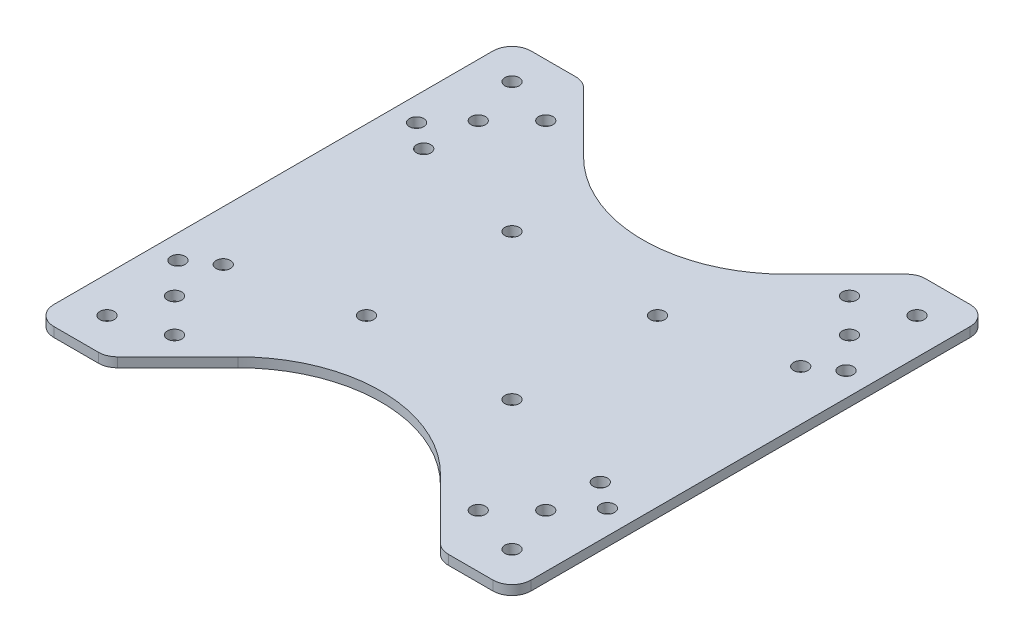
SolidWorks part; units mm, degrees
material "Thornel Mat VMA"
ref_plane "前视基准面" through (0, 0, 0) normal (0, 0, 1) x (1, 0, 0)
ref_plane "上视基准面" through (0, 0, 0) normal (0, 1, 0) x (1, 0, 0)
ref_plane "右视基准面" through (0, 0, 0) normal (1, 0, 0) x (0, 0, -1)
other "Configuration Table"
sketch "草图1" plane through (0, 0, 0) normal (0, 1, 0) x (1, 0, 0)
  line L1 (-50, -50) -> (50, -50)
  line L2 (-50, -50) -> (-50, 50)
  line L3 (-50, 50) -> (50, 50)
  line L4 (50, -50) -> (50, 50)
  line L5 (-50, -50) -> (50, 50) construction
  line L6 (-50, 50) -> (50, -50) construction
  point P0 (0, 0)
  dimension "D1" = 100
  dimension "D2" = 100
extrude "凸台-拉伸1" add sketch "草图1" along normal blind 2
sketch "草图3" plane through (0, 2, 0) normal (0, 1, 0) x (1, 0, 0)
  line L0 (-1000, 0) -> (49000, 0) construction
  line L1 (-42.4264, 42.4264) -> (0, 0) construction
  line L2 (-42.9749, 27.7358) -> (35312.3642, 35383.0749) construction
  line L3 (0, -1000) -> (0, 49000) construction
  circle A0 centre (0, 0) radius 60 construction
  circle A1 centre (-42.4264, 42.4264) radius 1.5
  circle A2 centre (-31.8198, 38.8909) radius 1.5
  circle A3 centre (-38.8909, 31.8198) radius 1.5
  circle A4 centre (-31.8198, -38.8909) radius 1.5
  circle A5 centre (-38.8909, -31.8198) radius 1.5
  circle A6 centre (-42.4264, -42.4264) radius 1.5
  circle A7 centre (31.8198, 38.8909) radius 1.5
  circle A8 centre (38.8909, 31.8198) radius 1.5
  circle A9 centre (42.4264, 42.4264) radius 1.5
  circle A10 centre (31.8198, -38.8909) radius 1.5
  circle A11 centre (42.4264, -42.4264) radius 1.5
  circle A12 centre (38.8909, -31.8198) radius 1.5
  dimension "D1" = 120
  dimension "D3" = 3
  dimension "D6" = 3
  dimension "D7" = 3
  dimension "D8" = 5
  dimension "D9" = 5
  dimension "D2" = 45
  dimension "D4" = 90
  dimension "D5" = 10
extrude "切除-拉伸2" cut sketch "草图3" against normal through all
sketch "草图4" plane through (0, 0, 0) normal (0, -1, 0) x (1, 0, 0)
  line L0 (0, -1000) -> (0, 49000) construction
  line L1 (-1000, 0) -> (49000, 0) construction
  circle A0 centre (-39.5, 21) radius 1.5
  circle A1 centre (39.5, 21) radius 1.5
  circle A2 centre (39.5, -21) radius 1.5
  circle A3 centre (-39.5, -21) radius 1.5
  dimension "D1" = 21
  dimension "D2" = 39.5
  dimension "D3" = 3
extrude "切除-拉伸3" cut sketch "草图4" against normal through all
sketch "草图5" plane through (0, 0, 0) normal (0, -1, 0) x (1, 0, 0)
  line L0 (-50, -50) -> (-50, 50) construction
  line L1 (-47, -20) -> (-45, -20)
  line L2 (-47, -20) -> (-47, 20)
  line L3 (-47, 20) -> (-45, 20)
  line L4 (-45, -20) -> (-45, 20)
  line L5 (-47, -20) -> (-45, 20) construction
  line L6 (-47, 20) -> (-45, -20) construction
  line L7 (0, -1000) -> (0, 49000) construction
  line L8 (47, 20) -> (45, 20)
  line L9 (45, -20) -> (45, 20)
  line L10 (47, -20) -> (45, -20)
  line L11 (47, -20) -> (47, 20)
  point P0 (-46, 0)
  dimension "D1" = 40
  dimension "D2" = 2
  dimension "D3" = 3
  dimension "D4" = 0
sketch "草图6" plane through (0, 0, 0) normal (0, -1, 0) x (1, 0, 0)
  line L0 (-1000, 0) -> (49000, 0) construction
  line L1 (-35, 50) -> (0, 15)
  line L2 (-50, 50) -> (50, 50) construction
  line L3 (0, 15) -> (35, 50)
  line L4 (35, 50) -> (-35, 50)
  line L5 (0, -15) -> (35, -50)
  line L6 (-35, -50) -> (0, -15)
  line L7 (35, -50) -> (-35, -50)
  dimension "D3" = 0
  dimension "D1" = 45
  dimension "D2" = 45
  dimension "D4" = 70
extrude "切除-拉伸6" cut sketch "草图6" against normal through all
fillet "圆角2" radius 30 2 edges at (0, 1, -15) (0, 1, 15)
sketch "草图7" plane through (0, 0, 0) normal (0, -1, 0) x (1, 0, 0)
  circle A0 centre (-15.25, 15.25) radius 1.5
  circle A1 centre (15.25, 15.25) radius 1.5
  circle A2 centre (15.25, -15.25) radius 1.5
  circle A3 centre (-15.25, -15.25) radius 1.5
  point P12 (0, 0)
  dimension "D1" = 15.25
  dimension "D2" = 3
  dimension "D3" = 15.25
  dimension "D4" = 4
extrude "切除-拉伸7" cut sketch "草图7" against normal through all
sketch "草图8" plane through (0, 0, 0) normal (0, -1, 0) x (1, 0, 0)
  line L0 (-1000, 0) -> (49000, 0) construction
  line L1 (0, -1000) -> (0, 49000) construction
  line L2 (-50, -50) -> (-50, 50) construction
  circle A0 centre (-45, 25) radius 1.5
  circle A1 centre (-45, -25) radius 1.5
  circle A2 centre (45, -25) radius 1.5
  circle A3 centre (45, 25) radius 1.5
  dimension "D1" = 3
  dimension "D2" = 5
  dimension "D3" = 25
extrude "切除-拉伸8" cut sketch "草图8" against normal through all
fillet "圆角3" radius 4 8 edges at (35, 1, 50) (50, 1, 50) (50, 1, -50) (35, 1, -50) (-35, 1, -50) (-50, 1, -50) (-35, 1, 50) (-50, 1, 50)
